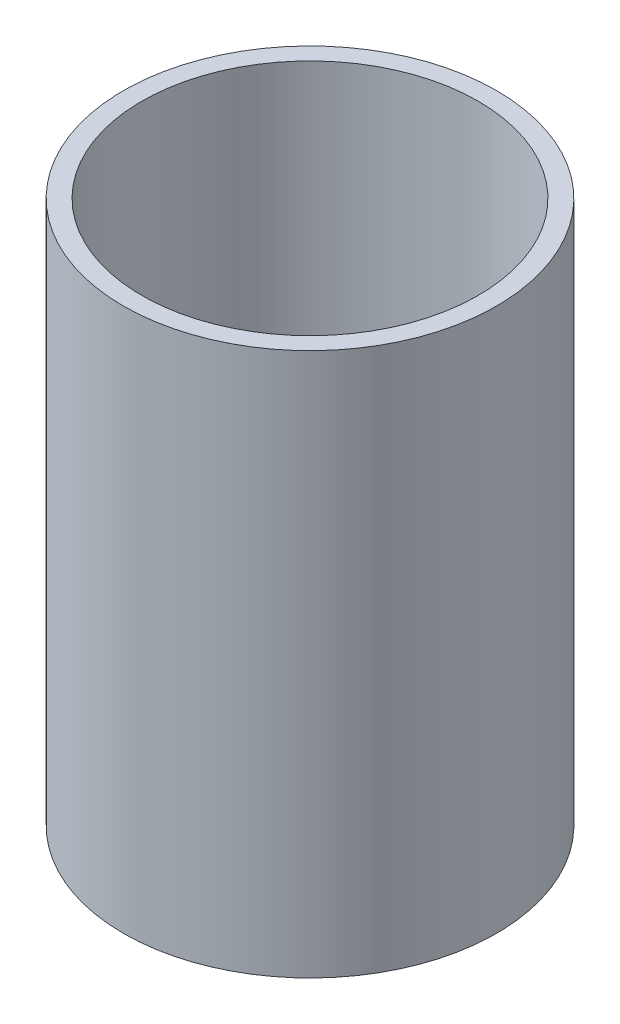
SolidWorks part; units mm, degrees
ref_plane "Front Plane" through (0, 0, 0) normal (0, 0, 1) x (1, 0, 0)
ref_plane "Top Plane" through (0, 0, 0) normal (0, 1, 0) x (1, 0, 0)
ref_plane "Right Plane" through (0, 0, 0) normal (1, 0, 0) x (0, 0, -1)
sketch "Sketch1" plane through (0, 0, 0) normal (0, 1, 0) x (1, 0, 0)
  circle A0 centre (0, 0) radius 42.5
  dimension "SLEEVE_OD" = 85
extrude "Boss-Extrude1" add sketch "Sketch1" along normal blind 123.7506
sketch "Sketch2" plane through (0, 0, 0) normal (0, 1, 0) x (1, 0, 0)
  circle A0 centre (0, 0) radius 38.3263
  dimension "BORE_D" = 76.6527
extrude "Cut-Extrude1" cut sketch "Sketch2" along normal through all
chamfer "Chamfer1" distance 3.7812 angle 45 rebuild error yes
